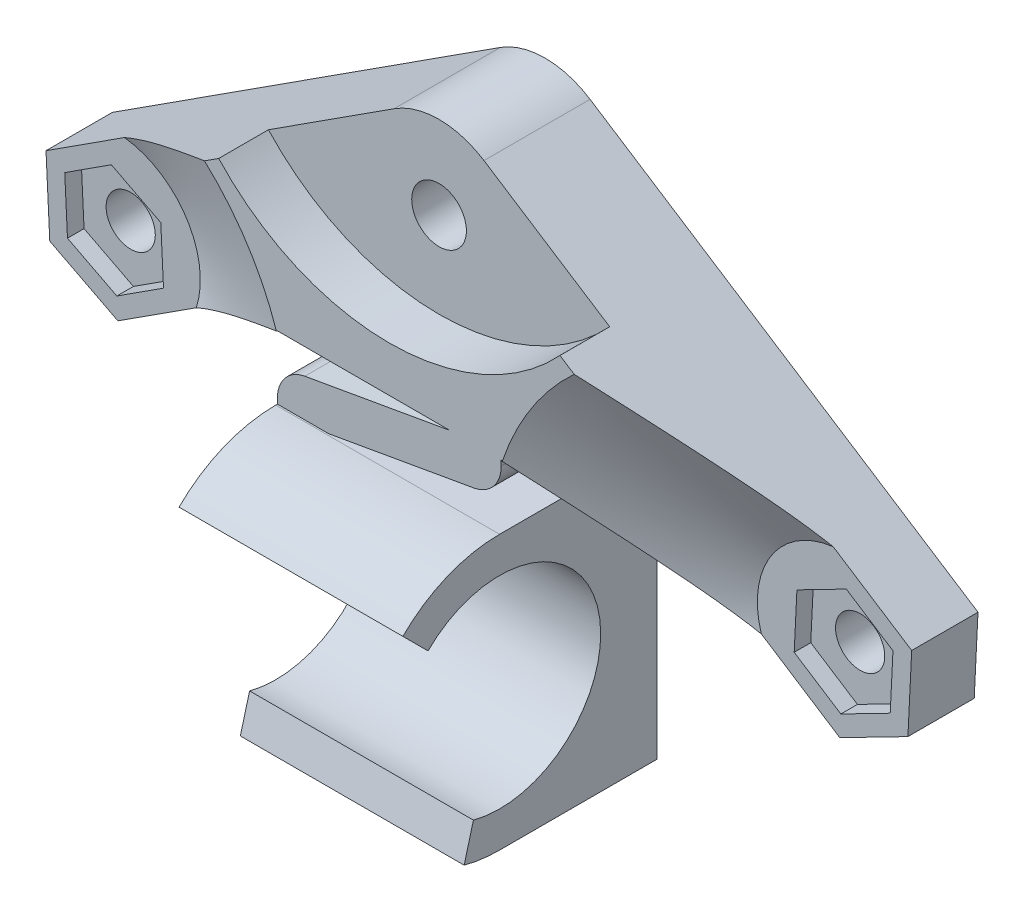
SolidWorks part; units mm, degrees
ref_plane "Front Plane" through (0, 0, 0) normal (0, 0, 1) x (1, 0, 0)
ref_plane "Top Plane" through (0, 0, 0) normal (0, 1, 0) x (1, 0, 0)
ref_plane "Right Plane" through (0, 0, 0) normal (1, 0, 0) x (0, 0, -1)
sketch "Sketch1" plane through (0, 0, 0) normal (-1, 0, 0) x (0, 0, 1)
  line L0 (-9.5, 8.25) -> (-9.5, -8.25)
  line L1 (0, 8.25) -> (-9.5, 8.25)
  line L2 (0, -8.25) -> (-9.5, -8.25)
  arc A4 (0, -8.25) -> (0, 8.25) centre (0, 0) ccw
  dimension "D2" = 16.5
  dimension "D3" = 9.5
extrude "Boss-Extrude1" add sketch "Sketch1" along normal blind 13.5
hole_wizard "Ø2.7 (2.7) Diameter Hole1" [suppressed] positions "Sketch5" profile "Sketch4" hole size "Ø2.7" standard "Ansi Metric"
sketch "Sketch5" [suppressed] plane through (-9.5, 0, 0) normal (-1, 0, 0) x (0, 0, 1)
  line L1 (2.5, -5) -> (11, -5) construction
  line L2 (2.5, -5) -> (2.5, 5) construction
  line L3 (2.5, 5) -> (11, 5) construction
  line L4 (11, -5) -> (11, 5) construction
  line L5 (0, 0) -> (2.5, 0) construction
  line L7 (-8.25, 0) -> (8.25, 0) construction
  line L10 (13.5, 0) -> (11, 0) construction
  line L11 (-8.25, 13.5) -> (8.25, 13.5) construction
  point P0 (2.5, -5)
  point P89 (2.5, 5)
  point P91 (11, 5)
  point P93 (11, -5)
  dimension "D1" = 2.5
  dimension "D2" = 10
sketch "Sketch4" plane through (-9.5, -5, 2.5) normal (0, 1, 0) x (0, 0, 1)
  line L0 (0, 0) -> (0, 4.8112)
  line L1 (0, 4.8112) -> (1.35, 4)
  line L2 (1.35, 4) -> (1.35, 0)
  line L5 (1.35, 0) -> (0, 0)
  line L10 (0, 4.8112) -> (-1.35, 4) construction
  line L11 (0, -6.35) -> (0, 107.95) construction
  dimension "Hole Dia." = 2.7
  dimension "Hole Depth" = 4
  dimension "Drill Angle" = 118
sketch "Sketch7" plane through (-13.5, 0, 0) normal (-1, 0, 0) x (0, 0, 1)
  line L0 (13.4819, 13.4819) -> (4.3134, 4.3134)
  line L1 (1.5788, -5.8921) -> (4.9347, -18.4166)
  line L2 (4.9347, -18.4166) -> (13.4819, 13.4819)
  line L3 (0, 0) -> (4.3134, 4.3134) construction
  line L4 (0, 0) -> (1.5788, -5.8921) construction
  line L5 (0, 0) -> (0, 14.6798) construction
  arc A0 (4.3134, 4.3134) -> (1.5788, -5.8921) centre (0, 0) ccw
  dimension "D3" = 6.1
  dimension "D1" = 120
  dimension "D2" = 45
extrude "Cut-Extrude1" cut sketch "Sketch7" against normal through all
ref_plane "Plane1" through (0, 0, -5.8921) normal (0, 0, -1) x (-1, 0, 0)
sketch "Sketch14" plane through (0, 0, -9.5) normal (0, 0, -1) x (-1, 0, 0)
  line L0 (6.75, -8.25) -> (6.75, 25.8362) construction
  line L1 (13.5, -8.25) -> (0, -8.25) construction
  line L2 (6.75, 7) -> (-15.25, 7) construction
  line L3 (4.0398, 24.2018) -> (-19.3588, 9.1097)
  line L4 (-17.4181, 10.3614) -> (-13.0819, 3.6386) construction
  line L5 (-15.0226, 2.3868) -> (0, 12.0764)
  line L6 (13.5, 8.25) -> (13.5, 12.0764)
  line L7 (0, 8.25) -> (0, 12.0764)
  line L8 (0, 8.25) -> (0, -8.25) construction
  line L9 (13.5, 8.25) -> (0, 8.25) construction
  line L10 (0, 8.25) -> (13.5, 8.25)
  line L12 (28.5226, 2.3868) -> (13.5, 12.0764)
  line L13 (9.4602, 24.2018) -> (32.8588, 9.1097)
  line L14 (-19.1315, 4.4965) -> (-15.0226, 2.3868)
  line L19 (-19.3588, 9.1097) -> (-19.1315, 4.4965)
  line L20 (32.6315, 4.4965) -> (32.8588, 9.1097)
  line L25 (28.5226, 2.3868) -> (32.6315, 4.4965)
  line L26 (24.6412, 4.8903) -> (28.5226, 2.3868) [skipped]
  line L27 (32.8588, 9.1097) -> (28.9774, 11.6132) [skipped]
  line L28 (28.9774, 11.6132) -> (24.8685, 9.5035) [skipped]
  line L29 (24.8685, 9.5035) -> (24.6412, 4.8903) [skipped]
  line L30 (-15.4774, 11.6132) -> (-19.3588, 9.1097) [skipped]
  line L31 (-15.0226, 2.3868) -> (-11.1412, 4.8903) [skipped]
  line L32 (-11.1412, 4.8903) -> (-11.3685, 9.5035) [skipped]
  line L33 (-11.3685, 9.5035) -> (-15.4774, 11.6132) [skipped]
  circle A0 centre (6.75, 20) radius 1.65
  arc A1 (9.4602, 24.2018) -> (4.0398, 24.2018) centre (6.75, 20) ccw
  circle A2 centre (-15.25, 7) radius 1.484
  circle A4 centre (28.75, 7) radius 1.484
  circle A6 centre (-15.25, 7) radius 4 construction
  circle A7 centre (28.75, 7) radius 4 construction
  point P24 (6.75, 8.25)
  dimension "D1" = 3.3
  dimension "D3" = 5
  dimension "D2" = 20
  dimension "D4" = 22
  dimension "D5" = 13
extrude "Boss-Extrude3" add sketch "Sketch14" against normal blind 9.4
sketch "Sketch15" plane through (0, 0, -0.1) normal (0, 0, 1) x (1, 0, 0)
  line L0 (0, 8.25) -> (-10.4017, 8.25)
  line L1 (0, 8.25) -> (-13.5, 8.25) construction
  line L2 (-10.4017, 8.25) -> (0, 10.0841)
  line L3 (0, 12.0764) -> (0, 8.25) construction
  line L4 (0, 10.0841) -> (0, 8.25)
  line L6 (-13.5, 8.25) -> (-13.5, 12.0764) construction
  line L7 (-13.5, 10.2423) -> (-13.5, 12.0764)
  line L8 (-13.5, 12.0764) -> (-3.0983, 12.0764)
  line L9 (-3.0983, 12.0764) -> (-13.5, 10.2423)
  dimension "D1" = 2.5
  dimension "D2" = 10
extrude "Cut-Extrude7" cut sketch "Sketch15" against normal through all
fillet "Fillet2" radius 2 2 edges at (0, 10.0841, -4.8) (-13.5, 10.2423, -4.8)
sketch "Sketch16" plane through (0, 0, -9.5) normal (0, 0, -1) x (-1, 0, 0)
  line L1 (6.75, 16.6514) -> (9.65, 18.3257)
  line L2 (9.65, 18.3257) -> (9.65, 21.6743)
  line L3 (9.65, 21.6743) -> (6.75, 23.3486)
  line L4 (6.75, 23.3486) -> (3.85, 21.6743)
  line L5 (3.85, 21.6743) -> (3.85, 18.3257)
  line L6 (3.85, 18.3257) -> (6.75, 16.6514)
  circle A0 centre (6.75, 20) radius 2.9 construction
  circle A1 centre (6.75, 20) radius 1.65 construction
  dimension "D1" = 5.8
extrude "Cut-Extrude8" cut sketch "Sketch16" against normal blind 4
sketch "Sketch17" plane through (0, 0, -0.1) normal (0, 0, 1) x (1, 0, 0)
  line L1 (19.1315, 4.4965) -> (19.3588, 9.1097)
  line L2 (19.3588, 9.1097) -> (17.4181, 10.3614)
  line L3 (-32.6315, 4.4965) -> (-28.5226, 2.3868)
  line L4 (-28.5226, 2.3868) -> (-26.5819, 3.6386)
  line L5 (13.0819, 3.6386) -> (15.0226, 2.3868)
  line L6 (15.0226, 2.3868) -> (19.1315, 4.4965)
  line L7 (13.423, 10.5584) -> (11.3685, 9.5035) [skipped]
  line L8 (11.2549, 7.1969) -> (11.1412, 4.8903) [skipped]
  line L11 (-30.9181, 10.3614) -> (-32.8588, 9.1097)
  line L12 (-32.8588, 9.1097) -> (-32.6315, 4.4965)
  line L13 (-24.6412, 4.8903) -> (-24.8685, 9.5035) [skipped]
  line L14 (-24.8685, 9.5035) -> (-28.9774, 11.6132) [skipped]
  arc A0 (-26.5819, 3.6386) -> (-30.9181, 10.3614) centre (-28.75, 7) ccw
  arc A1 (17.4181, 10.3614) -> (13.0819, 3.6386) centre (15.25, 7) ccw
  circle A2 centre (15.25, 7) radius 4 construction
  circle A3 centre (-28.75, 7) radius 4 construction
extrude "Cut-Extrude9" cut sketch "Sketch17" against normal offset from surface (5.4 mm away) 4 up to face at (-6.75, 20, -9.5)
chamfer "Chamfer2" distance 12 distance2 6 1 edges at (-25.3886, 9.1681, -0.1) first distance on face at (-8.4, 20, -0.1)
chamfer "Chamfer3" distance 12 distance2 6 1 edges at (11.8886, 9.1681, -0.1) first distance on face at (-8.4, 20, -0.1)
sketch "Sketch18" plane through (0, 0, -0.1) normal (0, 0, 1) x (1, 0, 0)
  line L0 (-6.75, 20) -> (-6.75, 28.8415) construction
  circle A0 centre (-6.75, 28.8415) radius 14.0267
extrude "Cut-Extrude10" cut sketch "Sketch18" against normal blind 3
sketch "Sketch19" plane through (0, 0, -5.5) normal (0, 0, 1) x (1, 0, 0)
  line L0 (-32.8588, 9.1097) -> (-28.1259, 12.1624) construction
  line L1 (-31.5641, 5.1849) -> (-28.5851, 3.6554)
  line L2 (-28.5851, 3.6554) -> (-25.7711, 5.4705)
  line L3 (-25.7711, 5.4705) -> (-25.9359, 8.8151)
  line L4 (-25.9359, 8.8151) -> (-28.9149, 10.3446)
  line L5 (-28.9149, 10.3446) -> (-31.7289, 8.5295)
  line L6 (-31.7289, 8.5295) -> (-31.5641, 5.1849)
  line L7 (18.0641, 5.1849) -> (18.2289, 8.5295)
  line L8 (18.2289, 8.5295) -> (15.4149, 10.3446)
  line L9 (15.4149, 10.3446) -> (12.4359, 8.8151)
  line L10 (12.4359, 8.8151) -> (12.2711, 5.4705)
  line L11 (12.2711, 5.4705) -> (15.0851, 3.6554)
  line L12 (15.0851, 3.6554) -> (18.0641, 5.1849)
  line L13 (14.6259, 12.1624) -> (19.3588, 9.1097) construction
  circle A0 centre (-28.75, 7) radius 2.9 construction
  circle A1 centre (15.25, 7) radius 2.9 construction
  circle A3 centre (-28.75, 7) radius 1.484 construction
  circle A4 centre (15.25, 7) radius 1.484 construction
  dimension "D1" = 5.8
extrude "Cut-Extrude11" cut sketch "Sketch19" against normal blind 1
